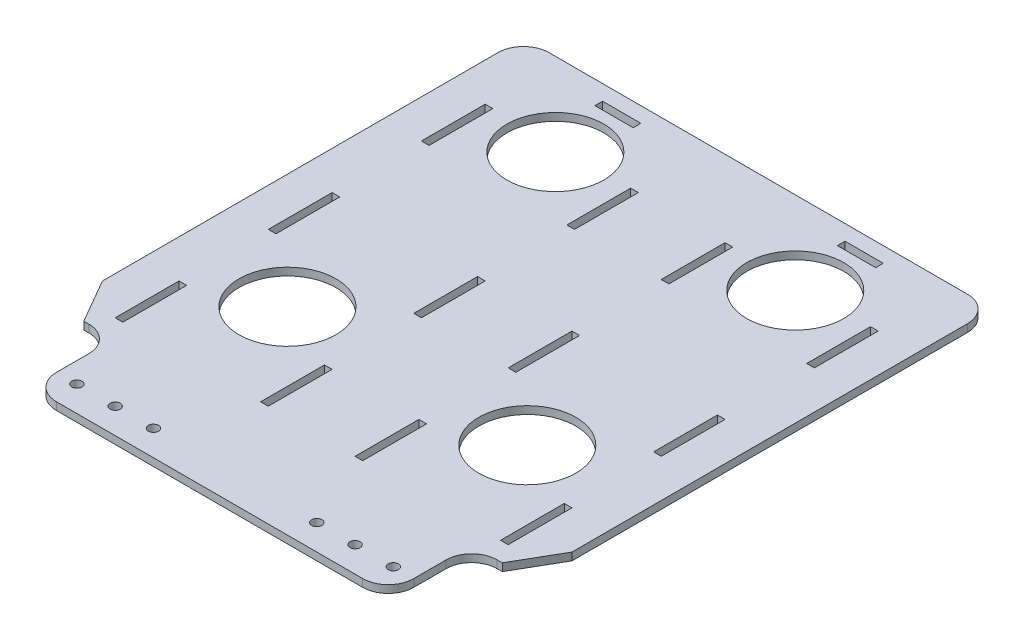
SolidWorks part; units mm, degrees
material "C-玻璃纤维"
ref_plane "前视基准面" through (0, 0, 0) normal (0, 0, 1) x (1, 0, 0)
ref_plane "上视基准面" through (0, 0, 0) normal (0, 1, 0) x (1, 0, 0)
ref_plane "右视基准面" through (0, 0, 0) normal (1, 0, 0) x (0, 0, -1)
other "Configuration Table"
sketch "草图1" plane through (0, 0, 0) normal (0, 1, 0) x (1, 0, 0)
  line L0 (47, 50) -> (47, -88.016) construction
  line L1 (-35, 37.5) -> (35, 37.5)
  line L2 (-35, 37.5) -> (-35, -37.5)
  line L3 (-35, -37.5) -> (35, -37.5)
  line L4 (35, 37.5) -> (35, -37.5)
  line L5 (-35, 37.5) -> (35, -37.5) construction
  line L6 (-35, -37.5) -> (35, 37.5) construction
  line L7 (0, 40) -> (0, -19.5313) construction
  line L8 (35, -37.5) -> (59, -37.5)
  line L9 (35, -37.5) -> (35, 37.5)
  line L10 (35, 37.5) -> (59, 37.5)
  line L11 (47, -37.5) -> (47, 37.5)
  line L12 (94, 40) -> (94, -19.5313) construction
  line L13 (129, -37.5) -> (59, 37.5) construction
  line L14 (129, 37.5) -> (59, -37.5) construction
  line L15 (59, -37.5) -> (59, 37.5)
  line L16 (59, 37.5) -> (59, -37.5)
  line L17 (129, -37.5) -> (59, -37.5)
  line L18 (129, 37.5) -> (129, -37.5)
  line L19 (129, 37.5) -> (59, 37.5)
  line L21 (-35, 37.5) -> (129, 37.5)
  line L22 (-35, 37.5) -> (-35, 177.5)
  line L23 (-35, 177.5) -> (129, 177.5)
  line L24 (129, 37.5) -> (129, 177.5)
  circle A0 centre (0, 40) radius 19
  circle A4 centre (94, 40) radius 19
  circle A5 centre (0, 145) radius 19
  circle A6 centre (94, 145) radius 19
  point P0 (0, 0)
  point P26 (94, 0)
  dimension "D3" = 38
  dimension "D4" = 40
  dimension "D8" = 105
  dimension "D1" = 70
  dimension "D2" = 75
  dimension "D5" = 140
  dimension "D6" = 12
  dimension "D7" = 2
extrude "凸台-拉伸1" add sketch "草图1" along normal blind 3 contours L19 A4 L24 L23 L22 L1 A0 L10 A5 A6 | A0 L1 L2 L3 L4 | L19 A4 L15 L17 L18 | L8 L11 L10 L4 | L8 L15 L10 L11 region at (47, 0, -107.2611) region at (0, 0, 3.0222) region at (41, 0, 0) region at (53, 0, 0) region at (94, 0, 3.0222)
sketch "草图2" plane through (0, 3, 0) normal (0, 1, 0) x (1, 0, 0)
  line L0 (-45, -27.5) -> (0, -27.5) construction
  line L1 (-35, -37.5) -> (129, -37.5) construction
  line L2 (0, -14.5781) -> (0, -41.2879) construction
  line L3 (47, 2.5) -> (47, -37.5) construction
  line L5 (94, -14.5781) -> (94, -41.2879) construction
  line L6 (139, -27.5) -> (94, -27.5) construction
  circle A0 centre (0, -27.5) radius 2
  circle A1 centre (-15, -27.5) radius 2
  circle A2 centre (15, -27.5) radius 2
  circle A3 centre (79, -27.5) radius 2
  circle A4 centre (109, -27.5) radius 2
  circle A5 centre (94, -27.5) radius 2
  dimension "D2" = 4
  dimension "D3" = 15
  dimension "D1" = 10
extrude "切除-拉伸1" cut sketch "草图2" against normal blind 3
sketch "草图3" plane through (0, 3, 0) normal (0, 1, 0) x (1, 0, 0)
  line L0 (-35, 177.5) -> (129, 177.5) construction
  line L1 (27, 147.5) -> (30, 147.5)
  line L2 (27, 147.5) -> (27, 122.5)
  line L3 (27, 122.5) -> (30, 122.5)
  line L4 (30, 147.5) -> (30, 122.5)
  line L5 (-35, -37.5) -> (-35, 177.5) construction
  line L6 (47, -37.5) -> (47, 12.5458) construction
  line L7 (-35, -37.5) -> (129, -37.5) construction
  line L8 (64, 147.5) -> (64, 122.5)
  line L9 (67, 122.5) -> (64, 122.5)
  line L10 (67, 147.5) -> (67, 122.5)
  line L11 (67, 147.5) -> (64, 147.5)
  line L12 (27, 87.5) -> (27, 62.5)
  line L13 (27, 87.5) -> (30, 87.5)
  line L14 (30, 87.5) -> (30, 62.5)
  line L15 (27, 62.5) -> (30, 62.5)
  line L16 (64, 87.5) -> (64, 62.5)
  line L17 (67, 62.5) -> (64, 62.5)
  line L18 (67, 87.5) -> (67, 62.5)
  line L19 (67, 87.5) -> (64, 87.5)
  line L20 (27, 27.5) -> (27, 2.5)
  line L21 (27, 27.5) -> (30, 27.5)
  line L22 (30, 27.5) -> (30, 2.5)
  line L23 (27, 2.5) -> (30, 2.5)
  line L24 (64, 27.5) -> (64, 2.5)
  line L25 (67, 2.5) -> (64, 2.5)
  line L26 (67, 27.5) -> (67, 2.5)
  line L27 (67, 27.5) -> (64, 27.5)
  line L28 (0, 147.1795) -> (0, 37.0423) construction
  line L29 (-27, 2.5) -> (-30, 2.5)
  line L30 (-30, 27.5) -> (-30, 2.5)
  line L31 (-27, 27.5) -> (-30, 27.5)
  line L32 (-27, 27.5) -> (-27, 2.5)
  line L33 (-27, 62.5) -> (-30, 62.5)
  line L34 (-30, 87.5) -> (-30, 62.5)
  line L35 (-27, 87.5) -> (-30, 87.5)
  line L36 (-27, 87.5) -> (-27, 62.5)
  line L37 (-30, 147.5) -> (-30, 122.5)
  line L38 (-27, 122.5) -> (-30, 122.5)
  line L39 (-27, 147.5) -> (-27, 122.5)
  line L40 (-27, 147.5) -> (-30, 147.5)
  line L41 (121, 147.5) -> (124, 147.5)
  line L42 (121, 147.5) -> (121, 122.5)
  line L43 (121, 122.5) -> (124, 122.5)
  line L44 (124, 147.5) -> (124, 122.5)
  line L45 (121, 87.5) -> (121, 62.5)
  line L46 (121, 87.5) -> (124, 87.5)
  line L47 (124, 87.5) -> (124, 62.5)
  line L48 (121, 62.5) -> (124, 62.5)
  line L49 (121, 27.5) -> (121, 2.5)
  line L50 (121, 27.5) -> (124, 27.5)
  line L51 (124, 27.5) -> (124, 2.5)
  line L52 (121, 2.5) -> (124, 2.5)
  dimension "D1" = 3
  dimension "D2" = 25
  dimension "D3" = 30
  dimension "D4" = 62
  dimension "D6" = 60
  dimension "D5" = 3
extrude "切除-拉伸2" cut sketch "草图3" against normal blind 10
sketch "草图4" plane through (0, 3, 0) normal (0, 1, 0) x (1, 0, 0)
  line L0 (-35, 177.5) -> (129, 177.5) construction
  line L1 (-8, 171.5) -> (7, 171.5)
  line L2 (-8, 171.5) -> (-8, 168.5)
  line L3 (-8, 168.5) -> (7, 168.5)
  line L4 (7, 171.5) -> (7, 168.5)
  line L5 (47, 177.5) -> (47, 163.5589) construction
  line L6 (102, 168.5) -> (87, 168.5)
  line L7 (87, 171.5) -> (87, 168.5)
  line L8 (102, 171.5) -> (87, 171.5)
  line L9 (102, 171.5) -> (102, 168.5)
  point P6 (47, 177.5)
  dimension "D1" = 3
  dimension "D2" = 15
  dimension "D3" = 40
  dimension "D4" = 6
extrude "切除-拉伸3" cut sketch "草图4" against normal blind 10
sketch "草图6" plane through (0, 3, 0) normal (0, 1, 0) x (1, 0, 0)
  line L0 (-35, -37.5) -> (-35, 177.5) construction
  line L1 (-35, 177.5) -> (-45, 177.5)
  line L2 (-35, 177.5) -> (-35, -12.5)
  line L3 (-35, -12.5) -> (-45, -12.5)
  line L4 (-45, 177.5) -> (-45, -12.5)
  line L5 (47, -37.5) -> (47, 41.2325) construction
  line L6 (-35, -37.5) -> (129, -37.5) construction
  line L7 (129, -12.5) -> (139, -12.5)
  line L8 (139, 177.5) -> (139, -12.5)
  line L9 (129, 177.5) -> (139, 177.5)
  line L10 (129, 177.5) -> (129, -12.5)
  dimension "D1" = 10
  dimension "D2" = 25
extrude "凸台-拉伸2" add sketch "草图6" against normal blind 3
chamfer "倒角1" distance 25 angle 30 2 edges at (139, 1.5, 12.5) (-45, 1.5, 12.5) first distance on face at (139, 1.5, -82.5) first distance on face at (-45, 1.5, -82.5)
fillet "圆角3" [suppressed] radius 20
fillet "圆角4" radius 10 4 edges at (-35, 1.5, 37.5) (129, 1.5, 37.5) (139, 1.5, -177.5) (-45, 1.5, -177.5)
sketch "草图7" plane through (0, 3, 0) normal (0, 1, 0) x (1, 0, 0)
  line L0 (47, -37.5) -> (47, -8.2967)
  line L1 (-23, -37.5) -> (-43, -37.5)
  line L2 (-23, -37.5) -> (-23, -4.8205)
  line L3 (-23, -4.8205) -> (-43, -4.8205)
  line L4 (-43, -37.5) -> (-43, -4.8205)
  line L5 (-25, -37.5) -> (119, -37.5) construction
  line L6 (117, -4.8205) -> (137, -4.8205)
  line L7 (137, -37.5) -> (137, -4.8205)
  line L8 (117, -37.5) -> (137, -37.5)
  line L9 (117, -37.5) -> (117, -4.8205)
  point P4 (-40.5, 0.3756)
  point P5 (-40.5, -1.9659)
  point P14 (0, 0)
  point P15 (0, 0)
  dimension "D2" = 70
  dimension "D3" = 20
extrude "切除-拉伸4" cut sketch "草图7" against normal blind 10 contours L4 L1 L2 L3 | L9 L8 L7 L6 region at (-33, 3, 21.1603) region at (127, 3, 21.1603)
fillet "圆角5" radius 10 2 edges at (117, 1.5, 37.5) (-23, 1.5, 37.5)
fillet "圆角6" radius 10 2 edges at (117, 1.5, 4.8205) (-23, 1.5, 4.8205)
fillet "圆角7" [suppressed] radius 5
